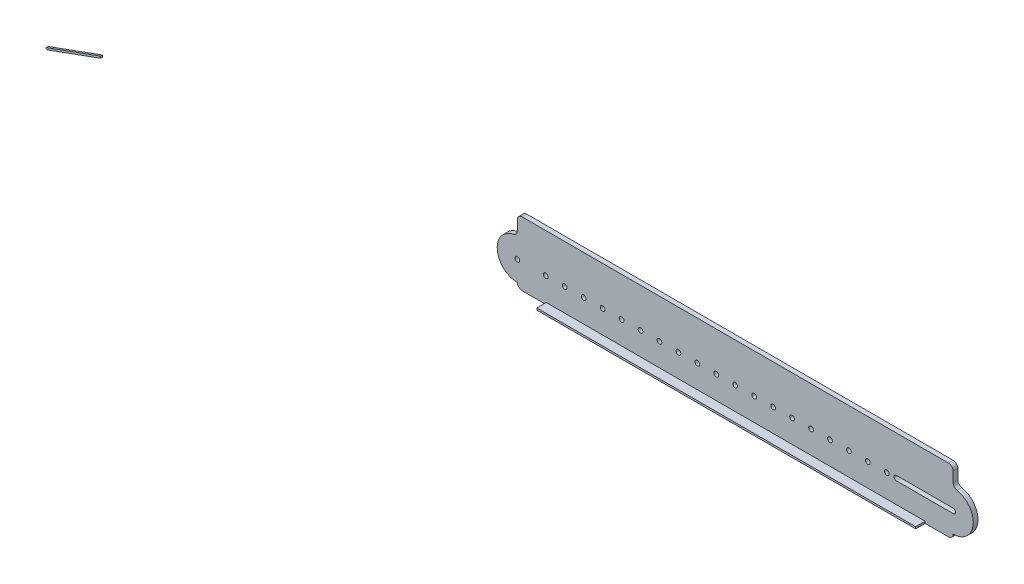
SolidWorks part; units mm, degrees
ref_plane "Front Plane" through (0, 0, 0) normal (0, 0, 1) x (1, 0, 0)
ref_plane "Top Plane" through (0, 0, 0) normal (0, 1, 0) x (1, 0, 0)
ref_plane "Right Plane" through (0, 0, 0) normal (1, 0, 0) x (0, 0, -1)
sketch "Sketch1" plane through (0, 0, 0) normal (0, 0, 1) x (1, 0, 0)
  line L0 (0, 26.9875) -> (584.2, 26.9875)
  line L1 (0, -26.9875) -> (584.2, -26.9875)
  line L2 (0, 26.9875) -> (584.2, 26.9875)
  line L3 (0, 26.9875) -> (0, 52.3875)
  line L4 (584.2, 26.9875) -> (584.2, 52.3875)
  line L5 (0, 52.3875) -> (584.2, 52.3875)
  line L6 (0, -26.9875) -> (584.2, -26.9875)
  line L7 (0, -26.9875) -> (0, -33.3375)
  line L8 (584.2, -26.9875) -> (584.2, -33.3375)
  line L9 (0, -33.3375) -> (584.2, -33.3375)
  arc A0 (0, 26.9875) -> (0, -26.9875) centre (0, 0) ccw
  arc A1 (584.2, -26.9875) -> (584.2, 26.9875) centre (584.2, 0) ccw
  dimension "D1" = 25.4
  dimension "D2" = 26.9875
  dimension "D3" = 584.2
  dimension "D4" = 6.35
extrude "Boss-Extrude1" add sketch "Sketch1" along normal mid plane 6.35 contours L5 L3 L0 L4 | L1 A1 L0 A0 | L6 L7 L9 L8 region at (292.1, 39.6875, 0) region at (292.1, 0, 0)
sketch "Sketch2" plane through (0, 0, 3.175) normal (0, 0, 1) x (1, 0, 0)
  line L3 (508, 3.175) -> (584.2, 3.175)
  line L4 (508, -3.175) -> (584.2, -3.175)
  arc A1 (584.2, -3.175) -> (584.2, 3.175) centre (584.2, 0) ccw
  arc A3 (508, 3.175) -> (508, -3.175) centre (508, 0) ccw
  circle A5 centre (0, 0) radius 3.175
  circle A6 centre (0, 0) radius 26.9875 construction
  circle A7 centre (38.1, 0) radius 3.175
  circle A8 centre (63.5, 0) radius 3.175
  circle A9 centre (88.9, 0) radius 3.175
  circle A10 centre (114.3, 0) radius 3.175
  circle A11 centre (139.7, 0) radius 3.175
  circle A12 centre (165.1, 0) radius 3.175
  circle A13 centre (190.5, 0) radius 3.175
  circle A14 centre (215.9, 0) radius 3.175
  circle A15 centre (241.3, 0) radius 3.175
  circle A16 centre (266.7, 0) radius 3.175
  circle A17 centre (292.1, 0) radius 3.175
  circle A18 centre (317.5, 0) radius 3.175
  circle A19 centre (342.9, 0) radius 3.175
  circle A20 centre (368.3, 0) radius 3.175
  circle A21 centre (393.7, 0) radius 3.175
  circle A22 centre (419.1, 0) radius 3.175
  circle A23 centre (444.5, 0) radius 3.175
  circle A24 centre (469.9, 0) radius 3.175
  circle A25 centre (495.3, 0) radius 3.175
  dimension "D1" = 38.1
  dimension "D2" = 19
extrude "Cut-Extrude1" cut sketch "Sketch2" against normal through all
fillet "Fillet1" radius 6.35 6 edges at (0, 26.9875, 0) (584.2, 26.9875, 0) (584.2, 52.3875, 0) (0, 52.3875, 0) (0, -33.3375, 0) (584.2, -33.3375, 0)
sketch "Sketch3" plane through (0, -33.3375, 0) normal (0, 1, 0) x (1, 0, 0)
  line L8 (38.707, -3.175) -> (546.707, -3.175)
  line L9 (6.35, -3.175) -> (577.85, -3.175) construction
  line L10 (38.707, -3.175) -> (38.707, -15.875)
  line L11 (546.707, -3.175) -> (546.707, -15.875)
  line L12 (38.707, -15.875) -> (546.707, -15.875)
  point P0 (292.707, -15.875)
  point P3 (292.707, -3.175)
  dimension "D1" = 508
  dimension "D2" = 12.7
extrude "Boss-Extrude2" add sketch "Sketch3" along normal blind 2.54
sketch "Sketch4" plane through (0, 0, 15.875) normal (0, 0, 1) x (1, 0, 0)
  line L0 (-38.1, -30.7975) -> (-38.1, -33.3375)
  line L5 (-546.1, -30.7975) -> (-546.1, -33.3375)
  line L6 (-546.1, -33.3375) -> (-617.5744, -59.3521)
  line L7 (-546.1, -30.7975) -> (-618.3908, -57.1092)
  line L8 (546.707, -30.7975) -> (38.707, -30.7975) construction
  arc A4 (-618.3908, -57.1092) -> (-617.5744, -59.3521) centre (-617.9826, -58.2306) ccw
  dimension "D3" = 46.0152
  dimension "D4" = 200
extrude "Boss-Extrude3" add sketch "Sketch4" against normal blind 2.54 contours L6 A4 L7 L5
